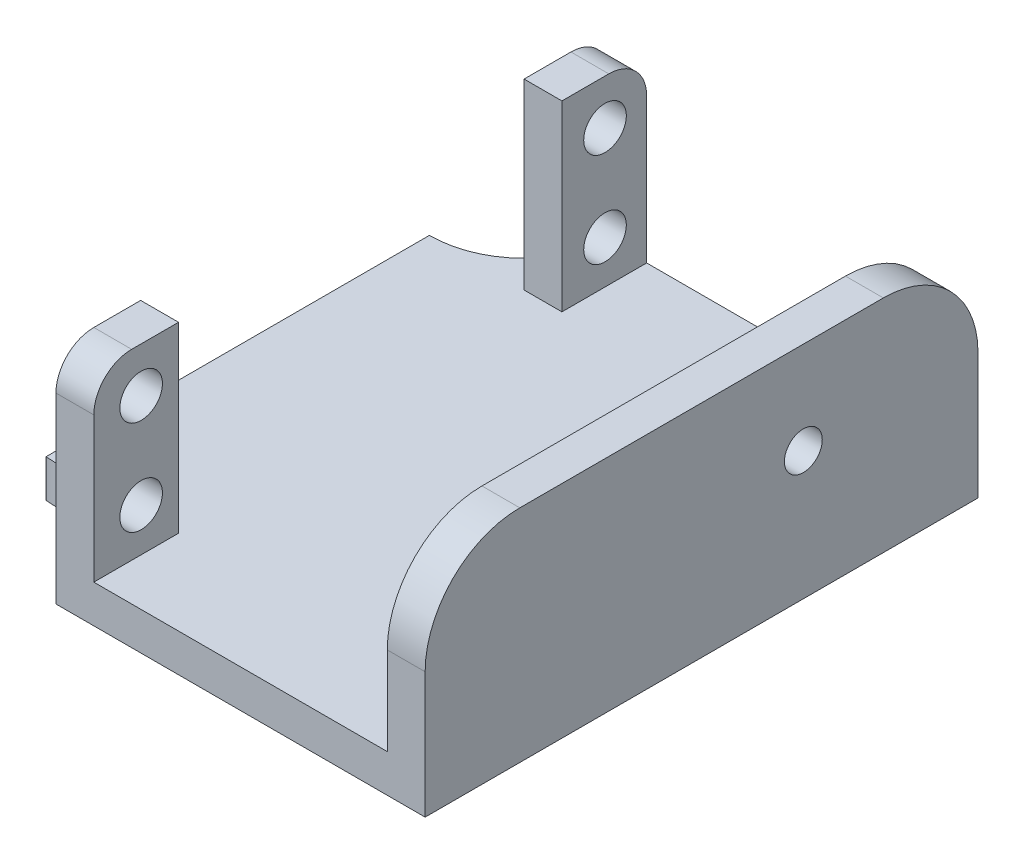
SolidWorks part; units mm, degrees
material "PLA"
ref_plane "Front Plane" through (0, 0, 0) normal (0, 0, 1) x (1, 0, 0)
ref_plane "Top Plane" through (0, 0, 0) normal (0, 1, 0) x (1, 0, 0)
ref_plane "Right Plane" through (0, 0, 0) normal (1, 0, 0) x (0, 0, -1)
sketch "Sketch1" plane through (0, 0, 0) normal (0, 1, 0) x (1, 0, 0)
  line L0 (-49, 49.45) -> (-39, 49.45)
  line L1 (-39, 49.45) -> (-39, 58.4)
  line L2 (-39, 58.4) -> (0, 58.4)
  line L3 (0, 58.4) -> (0, 0)
  line L4 (0, 0) -> (-39, 0)
  line L5 (-39, 0) -> (-39, 8.95)
  line L6 (-39, 8.95) -> (-49, 8.95)
  line L7 (-49, 8.95) -> (-49, 49.45)
  dimension "D1" = 58.4
  dimension "D2" = 49
  dimension "D3" = 10
  dimension "D4" = 8.95
  dimension "D5" = 8.95
extrude "Boss-Extrude1" add sketch "Sketch1" along normal blind 4
sketch "Sketch2" plane through (-39, 0, 0) normal (-1, 0, 0) x (0, 0, 1)
  line L0 (-58.4, 4) -> (-49.45, 4) construction
  line L1 (-8.95, 23.3) -> (0, 23.3)
  line L2 (-8.95, 23.3) -> (-8.95, 4)
  line L3 (-8.95, 4) -> (0, 4)
  line L4 (0, 23.3) -> (0, 4)
  line L5 (-58.4, 23.3) -> (-49.45, 23.3)
  line L6 (-58.4, 23.3) -> (-58.4, 4)
  line L7 (-58.4, 4) -> (-49.45, 4)
  line L8 (-49.45, 23.3) -> (-49.45, 4)
  line L9 (-58.4, 4) -> (-58.4, 0) construction
  line L10 (-49.45, 4) -> (-49.45, 0) construction
  line L11 (-8.95, 4) -> (0, 4) construction
  line L12 (0, 4) -> (0, 0) construction
  line L13 (-8.95, 4) -> (-8.95, 0) construction
  line L14 (-49.45, 4) -> (-8.95, 4) construction
  circle A0 centre (-5, 18.55) radius 2.25
  circle A1 centre (-5, 8.55) radius 2.25
  circle A2 centre (-54, 18.55) radius 2.25
  circle A3 centre (-54, 8.55) radius 2.25
  dimension "D1" = 4.5
  dimension "D2" = 4.5
  dimension "D8" = 4.5
  dimension "D9" = 4.5
  dimension "D3" = 19.3
  dimension "D4" = 10
  dimension "D5" = 4.55
  dimension "D6" = 4.55
  dimension "D7" = 4.55
  dimension "D10" = 3.95
extrude "Boss-Extrude2" add sketch "Sketch2" against normal blind 4
fillet "Fillet1" radius 10 2 edges at (-39, 2, -49.45) (-39, 2, -8.95)
fillet "Fillet2" radius 4 2 edges at (-37, 23.3, -58.4) (-37, 23.3, 0)
sketch "Sketch3" plane through (0, 0, 0) normal (1, 0, 0) x (0, 0, -1)
  line L0 (0, 4) -> (58.4, 4) construction
  line L1 (0, 23.3) -> (58.4, 23.3)
  line L2 (0, 23.3) -> (0, 4)
  line L3 (0, 4) -> (58.4, 4)
  line L4 (58.4, 23.3) -> (58.4, 4)
  line L5 (0, 4) -> (0, 0) construction
  line L6 (58.4, 4) -> (58.4, 0) construction
  circle A0 centre (39.95, 13.55) radius 2
  dimension "D4" = 4
  dimension "D1" = 19.3
  dimension "D2" = 18.45
  dimension "D3" = 9.55
extrude "Boss-Extrude3" add sketch "Sketch3" against normal blind 4
fillet "Fillet3" radius 10 2 edges at (-2, 23.3, 0) (-2, 23.3, -58.4)
sketch "Sketch4" plane through (-49, 0, 0) normal (-1, 0, 0) x (0, 0, 1)
  line L0 (-49.45, 4) -> (-8.95, 4) construction
  line L1 (-49.45, 4) -> (-8.95, 4)
  line L2 (-49.45, 4) -> (-49.45, 3.5)
  line L3 (-49.45, 3.5) -> (-8.95, 3.5)
  line L4 (-8.95, 4) -> (-8.95, 3.5)
  line L5 (-49.45, 4) -> (-49.45, 0) construction
  line L6 (-8.95, 4) -> (-8.95, 0) construction
  dimension "D1" = 0.5
extrude "Cut-Extrude1" [suppressed] cut sketch "Sketch4" against normal up to surface (45 mm away)
